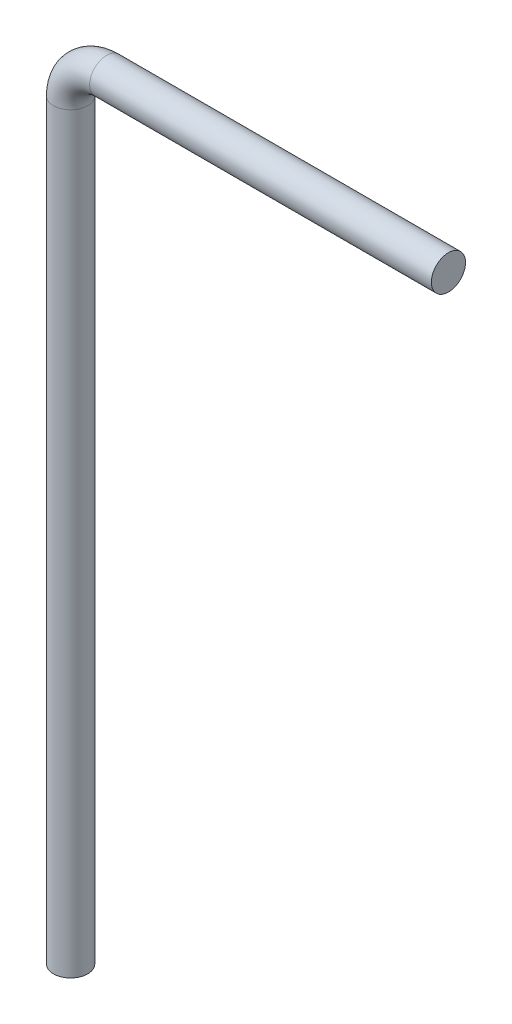
SolidWorks part; units mm, degrees
material "Titânio Ti-13V-11Cr-3Al tratado com solução"
ref_plane "Plano frontal" through (0, 0, 0) normal (0, 0, 1) x (1, 0, 0)
ref_plane "Plano superior" through (0, 0, 0) normal (0, 1, 0) x (1, 0, 0)
ref_plane "Plano direito" through (0, 0, 0) normal (1, 0, 0) x (0, 0, -1)
sketch "Esboço1" plane through (0, 0, 0) normal (0, 0, 1) x (1, 0, 0)
  line L0 (0, 55) -> (0, -55)
  line L1 (5.2783, 60.2783) -> (55.2783, 60.2783)
  arc A0 (0, 55) -> (5.2783, 60.2783) centre (5.2783, 55) cw
  point P4 (0, 0)
  dimension "D1" = 110
  dimension "D2" = 50
sketch "Esboço2" plane through (0, 0, 0) normal (0, 1, 0) x (1, 0, 0)
  circle A0 centre (0, 0) radius 3
  dimension "D1" = 6
sweep "Varredura1" add path "Esboço1" circular profile diameter 5 parameters "D3"=5
